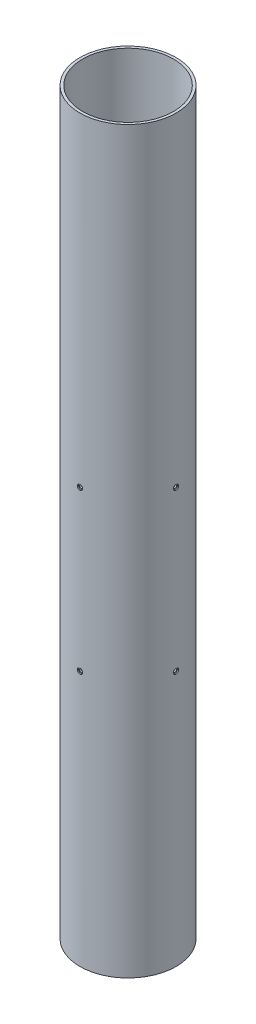
SolidWorks part; units mm, degrees
material "Hexcel AS4C (3000 Filaments)"
ref_plane "Front Plane" through (0, 0, 0) normal (0, 0, 1) x (1, 0, 0)
ref_plane "Top Plane" through (0, 0, 0) normal (0, 1, 0) x (1, 0, 0)
ref_plane "Right Plane" through (0, 0, 0) normal (1, 0, 0) x (0, 0, -1)
sketch "Sketch1" plane through (0, 0, 0) normal (0, 1, 0) x (1, 0, 0)
  circle A0 centre (0, 0) radius 50.8
  dimension "D1" = 101.6
extrude "Tube Extrusion" add sketch "Sketch1" along normal blind 825.5 thin thin type one direction wall 2.921
ref_plane "Hole Plane" through (0, 0, 53.721) normal (0, 0, 1) x (1, 0, 0)
sketch "Sketch3" plane through (0, 0, 53.721) normal (0, 0, 1) x (1, 0, 0)
  line L0 (0, 825.5) -> (0, 0) construction
  line L1 (50.8, 825.5) -> (-50.8, 825.5) construction
  line L2 (53.721, 825.5) -> (-53.721, 825.5) construction
  circle A0 centre (0, 463.55) radius 1.6383
  circle A1 centre (0, 285.75) radius 1.6383
  dimension "D1" = 3.2766
  dimension "D3" = 3.2766
  dimension "D2" = 361.95
  dimension "D4" = 539.75
extrude "Bulkhead Holes" cut sketch "Sketch3" against normal up to next
pattern_circular "Hole Pattern" count 4 over 360 about axis through (0, 825.5, 0) along (0, -1, 0) of "Bulkhead Holes" reverse direction yes
sketch "Sketch4" plane through (0, 0, 53.721) normal (0, 0, 1) x (1, 0, 0)
  circle A0 centre (0, 285.75) radius 1.6383 construction
  circle A1 centre (0, 463.55) radius 1.6383 construction
  circle A3 centre (0, 285.75) radius 1.6383
  circle A4 centre (0, 463.55) radius 1.6383
  circle A7 centre (0, 463.55) radius 2.9083
  circle A8 centre (0, 285.75) radius 2.9083
  dimension "D2" = 1.27
extrude "Cut-Extrude1" cut sketch "Sketch4" against normal blind 1.27
pattern_circular "CirPattern1" count 4 over 360 about axis through (0, 825.5, 0) along (0, -1, 0) of "Cut-Extrude1"
